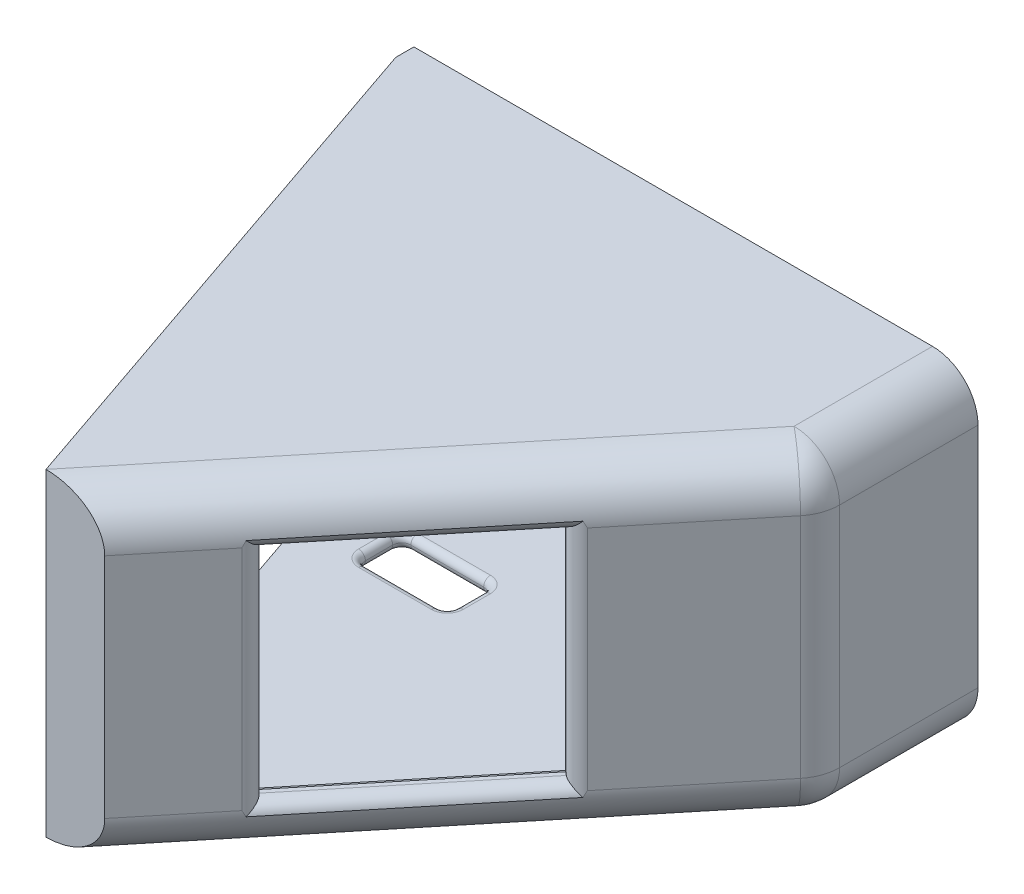
SolidWorks part; units mm, degrees
note: The reader was unsure of these and kept them because the rebuilt part matched: shared geometry of "草图1<5>".
ref_plane "前视基准面" through (0, 0, 0) normal (0, 0, 1) x (1, 0, 0)
ref_plane "上视基准面" through (0, 0, 0) normal (0, 1, 0) x (1, 0, 0)
ref_plane "右视基准面" through (0, 0, 0) normal (1, 0, 0) x (0, 0, -1)
sketch "草图1" plane through (0, 0, 0) normal (0, 0, 1) x (1, 0, 0)
  line L1 (-26, -14.5) -> (26, -14.5)
  line L2 (-26, -14.5) -> (-26, 14.5)
  line L3 (-26, 14.5) -> (26, 14.5)
  line L4 (26, -14.5) -> (26, 14.5)
  line L5 (0, 14.5) -> (0, -14.5) construction
  line L6 (-26, 0) -> (26, 0) construction
  circle A0 centre (-23.18, 11.685) radius 1.45
  circle A2 centre (-23.18, -11.685) radius 1.45
  circle A3 centre (23.18, -11.685) radius 1.45
  circle A4 centre (23.18, 11.685) radius 1.45
  point P0 (0, 0)
  dimension "D3" = 11.685
  dimension "D4" = 2.82
  dimension "D5" = 2.9
  dimension "D1" = 29
  dimension "D2" = 52
extrude "凸台-拉伸4" add sketch "草图1" along normal blind 6 contours A2 | A0 | A4 | A3
extrude "凸台-拉伸5" add sketch "草图1<5>" against normal blind 2 contours L3 L4 L1 L2
sketch "草图1<5>" plane through (0, 0, 0) normal (0, 0, 1) x (1, 0, 0) same geometry as "草图1"
sketch "草图5" plane through (0, 0, 0) normal (0, 0, 1) x (1, 0, 0)
  line L8 (-29, 17.5) -> (-29, -17.5)
  line L9 (-29, -17.5) -> (29, -17.5)
  line L10 (29, -17.5) -> (29, 17.5)
  line L11 (29, 17.5) -> (-29, 17.5)
  line L12 (-29, 17.5) -> (-29, -17.5)
  line L13 (-29, -17.5) -> (29, -17.5)
  line L14 (29, -17.5) -> (29, 17.5)
  line L15 (29, 17.5) -> (-29, 17.5)
  dimension "D1" = 3
extrude "凸台-拉伸6" add sketch "草图5" against normal blind 2
sketch "草图6" plane through (0, 0, 0) normal (0, 0, 1) x (1, 0, 0)
  line L0 (29, 17.5) -> (29, -17.5)
  line L1 (29, 17.5) -> (-29, 17.5) construction
  line L2 (-29, -17.5) -> (29, -17.5) construction
  line L3 (29, -17.5) -> (29, 17.5) construction
  line L4 (29, 17.5) -> (33, 17.5)
  line L5 (33, 17.5) -> (33, -17.5)
  line L6 (33, -17.5) -> (29, -17.5)
  line L8 (29, 17.5) -> (-29, 17.5)
  line L9 (-29, 17.5) -> (-29, -17.5)
  line L10 (-29, -17.5) -> (29, -17.5)
  line L11 (29, -17.5) -> (29, 17.5)
  line L12 (29, 17.5) -> (-29, 17.5)
  line L13 (-29, 17.5) -> (-29, -17.5)
  line L14 (-29, -17.5) -> (29, -17.5)
  line L16 (33, -17.5) -> (29, -17.5)
  line L17 (33, -17.5) -> (33, 17.5)
  line L18 (33, 17.5) -> (29, 17.5)
  line L19 (29, -17.5) -> (29, 17.5)
  dimension "D1" = 4
  dimension "D2" = 0
extrude "凸台-拉伸7" add sketch "草图6" along normal blind 12 contours L17 L16 L19 L18
fillet "圆角1" radius 1.33 1 edges at (-24.63, 11.685, 0)
fillet "圆角2" radius 1.33 1 edges at (-24.63, -11.685, 0)
fillet "圆角3" radius 1.33 1 edges at (21.73, -11.685, 0)
fillet "圆角4" radius 1.33 1 edges at (21.73, 11.685, 0)
sketch "草图11" plane through (0, 0, 12) normal (0, 0, 1) x (1, 0, 0)
  line L0 (33, -17.5) -> (29, -17.5) construction
  line L1 (33, 17.5) -> (32.1154, 17.5)
  line L2 (33, 17.5) -> (33, -17.5)
  line L3 (33, -17.5) -> (32.1154, -17.5)
  line L4 (32.1154, 17.5) -> (32.1154, -17.5)
extrude "凸台-拉伸8" add sketch "草图11" along normal blind 3
sketch "草图12" plane through (0, -17.5, 0) normal (0, -1, 0) x (-1, 0, 0)
  line L0 (-29, -12) -> (9.0007, -58.4321)
  line L1 (-33, -15) -> (2.5455, -58.4321)
  line L2 (9.0007, -58.4321) -> (2.5455, -58.4321)
  line L3 (-33, -15) -> (-32.1154, -15)
  line L4 (-32.1154, -15) -> (-32.1154, -12)
  line L5 (-32.1154, -12) -> (-29, -12)
  dimension "D1" = 60
extrude "凸台-拉伸9" add sketch "草图12" against normal through all
sketch "草图14" plane through (23.2488, 0, 19.0272) normal (-0.7739, 0, -0.6333) x (-0.6333, 0, 0.7739)
  line L0 (50.9194, -17.5) -> (-9.0806, 17.5) construction
  line L1 (-9.0806, 17.5) -> (50.9194, 17.5) construction
  line L2 (50.9194, 17.5) -> (-9.0806, -17.5) construction
  line L4 (40.9194, 14) -> (0.9194, 14)
  line L5 (40.9194, 14) -> (40.9194, -14)
  line L6 (40.9194, -14) -> (0.9194, -14)
  line L7 (0.9194, 14) -> (0.9194, -14)
  line L8 (20.9194, -14) -> (20.9194, 14) construction
  line L9 (40.9194, 0) -> (0.9194, 0) construction
  point P4 (20.9194, 0)
  dimension "D1" = 40
  dimension "D2" = 28
extrude "切除-拉伸1" cut sketch "草图14" against normal blind 1.4
sketch "草图15" plane through (24.3323, 0, 19.9139) normal (-0.7739, 0, -0.6333) x (-0.6333, 0, 0.7739)
  line L0 (40.9194, -14) -> (0.9194, 14) construction
  line L1 (0.9194, 14) -> (40.9194, 14)
  line L2 (40.9194, 14) -> (0.9194, -14) construction
  line L3 (40.9194, -14) -> (40.9194, 14) construction
  line L4 (36.0294, 14) -> (4.5294, 14)
  line L5 (36.0294, 14) -> (36.0294, -14)
  line L6 (36.0294, -14) -> (4.5294, -14)
  line L7 (4.5294, 14) -> (4.5294, -14)
  line L9 (0.9194, -14) -> (40.9194, -14) construction
  dimension "D1" = 4.89
  dimension "D2" = 31.5
extrude "切除-拉伸2" cut sketch "草图15" against normal blind 1.6 contours L5 L4 L7 L6
sketch "草图16" plane through (25.5705, 0, 20.9272) normal (-0.7739, 0, -0.6333) x (-0.6333, 0, 0.7739)
  line L0 (36.0294, 14) -> (36.0294, -14) construction
  line L1 (34.6294, 12) -> (10.6294, 12)
  line L2 (34.6294, 12) -> (34.6294, -12)
  line L3 (34.6294, -12) -> (10.6294, -12)
  line L4 (10.6294, 12) -> (10.6294, -12)
  line L5 (22.6294, -12) -> (22.6294, 12) construction
  line L6 (34.6294, 0) -> (10.6294, 0) construction
  line L7 (36.0294, 0) -> (4.5294, 0) construction
  line L8 (4.5294, 14) -> (4.5294, -14) construction
  point P0 (22.6294, 0)
  dimension "D1" = 24
  dimension "D2" = 24
  dimension "D3" = 1.4
extrude "切除-拉伸3" cut sketch "草图16" against normal through all contours L2 L1 L4 L3
sketch "草图17" plane through (24.3323, 0, 19.9139) normal (-0.7739, 0, -0.6333) x (-0.6333, 0, 0.7739)
  line L1 (40.9194, 14) -> (38.4194, 14)
  line L2 (40.9194, 14) -> (40.9194, -14)
  line L3 (40.9194, -14) -> (38.4194, -14)
  line L4 (38.4194, 14) -> (38.4194, -14)
  line L5 (40.9194, 14) -> (36.0294, 14) construction
  line L6 (36.0294, -14) -> (40.9194, -14) construction
  line L7 (40.9194, -14) -> (40.9194, 14) construction
  dimension "D1" = 2.5
extrude "切除-拉伸4" cut sketch "草图17" against normal blind 2
fillet "圆角5" radius 5 1 edges at (33, 0, 15)
sketch "草图18" plane through (0, -17.5, 0) normal (0, -1, 0) x (1, 0, 0)
  line L1 (33, 0) -> (29, 0)
  line L2 (33, 0) -> (33, -2)
  line L3 (33, -2) -> (29, -2)
  line L4 (29, 0) -> (29, -2)
extrude "凸台-拉伸10" add sketch "草图18" against normal through all
fillet "圆角6" radius 5 1 edges at (29, 0, 12)
sketch "草图19" plane through (0, -17.5, 0) normal (0, -1, 0) x (1, 0, 0)
  line L0 (-9.0007, 58.4321) -> (-29, 0)
  line L1 (-29, 0) -> (29, 0)
  line L10 (29, 10.2148) -> (29, 0)
  line L11 (29, 0) -> (-29, 0)
  line L12 (-29, 0) -> (-29, -2)
  line L13 (-29, -2) -> (33, -2)
  line L14 (33, -2) -> (33, 13.2148)
  line L15 (31.8693, 16.3815) -> (-2.5455, 58.4321)
  line L16 (-2.5455, 58.4321) -> (-9.0007, 58.4321)
  line L17 (-9.0007, 58.4321) -> (27.8693, 13.3815)
  line L18 (29, 10.2148) -> (29, 0)
  line L25 (-9.0007, 58.4321) -> (27.8693, 13.3815)
  arc A2 (29, 10.2148) -> (27.8693, 13.3815) centre (24, 10.2148) ccw
  arc A3 (33, 13.2148) -> (31.8693, 16.3815) centre (28, 13.2148) ccw
  arc A4 (29, 10.2148) -> (27.8693, 13.3815) centre (24, 10.2148) ccw
  dimension "D1" = 0
extrude "凸台-拉伸11" add sketch "草图19" against normal blind 1.5
fillet "圆角7" radius 5 4 edges at (33, -17.5, 5.6074) (32.7089, -17.5, 14.8961) (14.6619, -17.5, 37.4068) (-5.7731, -17.5, 58.4321)
fillet "圆角9" radius 1.5 4 edges at (20.3826, 0, 30.4168) (12.7825, 12, 39.7033) (12.7825, -12, 39.7033) (5.1823, 0, 48.9897)
sketch "草图22" plane through (0, 17.5, 0) normal (0, 1, 0) x (1, 0, 0)
  line L0 (-9.0007, -58.4321) -> (-29, 0)
  line L1 (-29, 0) -> (29, 0)
  line L10 (-29, 0) -> (29, 0)
  line L11 (29, 0) -> (29, -10.2148)
  line L12 (27.8693, -13.3815) -> (-9.0007, -58.4321)
  line L13 (-9.0007, -58.4321) -> (-2.5455, -58.4321)
  line L14 (-2.5455, -58.4321) -> (31.8693, -16.3815)
  line L15 (33, -13.2148) -> (33, 2)
  line L16 (33, 2) -> (-29, 2)
  line L17 (-29, 2) -> (-29, 0)
  line L18 (-29, 0) -> (29, 0)
  line L21 (-9.0007, -58.4321) -> (-2.5455, -58.4321)
  line L22 (-2.5455, -58.4321) -> (31.8693, -16.3815)
  line L23 (33, -13.2148) -> (33, 2)
  line L24 (33, 2) -> (-29, 2)
  line L25 (-29, 2) -> (-29, 0)
  arc A2 (27.8693, -13.3815) -> (29, -10.2148) centre (24, -10.2148) ccw
  arc A3 (31.8693, -16.3815) -> (33, -13.2148) centre (28, -13.2148) ccw
  arc A5 (31.8693, -16.3815) -> (33, -13.2148) centre (28, -13.2148) ccw
  dimension "D1" = 0
extrude "凸台-拉伸15" add sketch "草图22" against normal blind 1.5 contours L0 L11 L10 L1
fillet "圆角10" radius 5 7 edges at (12.7825, 13.5, 39.7033) (4.5641, 12.4393, 49.0514) (20.3209, 12.4393, 29.7986) (33, 17.5, 5.6074) (14.6619, 17.5, 37.4068) (32.7089, 17.5, 14.8961) (-5.7731, 17.5, 58.4321)
sketch "草图26" plane through (0, 0, 0) normal (0, 0, 1) x (1, 0, 0)
  line L0 (11.2453, 5.8634) -> (13.0914, 7.3757)
  line L1 (15.0126, 6.706) -> (17.2453, 5.8634)
  line L2 (17.2453, 5.8634) -> (19.0914, 7.3757)
  line L3 (19.0914, 7.3757) -> (18.7048, 9.7306)
  line L4 (18.7048, 9.7306) -> (16.472, 10.5732)
  line L5 (16.472, 10.5732) -> (14.6259, 9.0609)
  line L6 (14.6259, 9.0609) -> (15.0126, 6.706)
  line L7 (9.0126, 6.706) -> (11.2453, 5.8634)
  line L8 (8.6259, 9.0609) -> (9.0126, 6.706)
  line L9 (10.472, 10.5732) -> (8.6259, 9.0609)
  line L10 (12.7048, 9.7306) -> (10.472, 10.5732)
  line L11 (13.0914, 7.3757) -> (12.7048, 9.7306)
  line L12 (5.2453, 5.8634) -> (7.0914, 7.3757)
  line L13 (3.0126, 6.706) -> (5.2453, 5.8634)
  line L14 (2.6259, 9.0609) -> (3.0126, 6.706)
  line L15 (4.472, 10.5732) -> (2.6259, 9.0609)
  line L16 (6.7048, 9.7306) -> (4.472, 10.5732)
  line L17 (7.0914, 7.3757) -> (6.7048, 9.7306)
  line L18 (-0.7547, 5.8634) -> (1.0914, 7.3757)
  line L19 (-2.9874, 6.706) -> (-0.7547, 5.8634)
  line L20 (-3.3741, 9.0609) -> (-2.9874, 6.706)
  line L21 (-1.528, 10.5732) -> (-3.3741, 9.0609)
  line L22 (0.7048, 9.7306) -> (-1.528, 10.5732)
  line L23 (1.0914, 7.3757) -> (0.7048, 9.7306)
  line L24 (-6.7547, 5.8634) -> (-4.9086, 7.3757)
  line L25 (-8.9874, 6.706) -> (-6.7547, 5.8634)
  line L26 (-9.3741, 9.0609) -> (-8.9874, 6.706)
  line L27 (-7.528, 10.5732) -> (-9.3741, 9.0609)
  line L28 (-5.2952, 9.7306) -> (-7.528, 10.5732)
  line L29 (-4.9086, 7.3757) -> (-5.2952, 9.7306)
  line L30 (-12.7547, 5.8634) -> (-10.9086, 7.3757)
  line L31 (-14.9874, 6.706) -> (-12.7547, 5.8634)
  line L32 (-15.3741, 9.0609) -> (-14.9874, 6.706)
  line L33 (-13.528, 10.5732) -> (-15.3741, 9.0609)
  line L34 (-11.2952, 9.7306) -> (-13.528, 10.5732)
  line L35 (-10.9086, 7.3757) -> (-11.2952, 9.7306)
  line L36 (11.2453, 0.8634) -> (13.0914, 2.3757)
  line L37 (9.0126, 1.706) -> (11.2453, 0.8634)
  line L38 (8.6259, 4.0609) -> (9.0126, 1.706)
  line L39 (10.472, 5.5732) -> (8.6259, 4.0609)
  line L40 (12.7048, 4.7306) -> (10.472, 5.5732)
  line L41 (13.0914, 2.3757) -> (12.7048, 4.7306)
  line L42 (5.2453, 0.8634) -> (7.0914, 2.3757)
  line L43 (3.0126, 1.706) -> (5.2453, 0.8634)
  line L44 (2.6259, 4.0609) -> (3.0126, 1.706)
  line L45 (4.472, 5.5732) -> (2.6259, 4.0609)
  line L46 (6.7048, 4.7306) -> (4.472, 5.5732)
  line L47 (7.0914, 2.3757) -> (6.7048, 4.7306)
  line L48 (-0.7547, 0.8634) -> (1.0914, 2.3757)
  line L49 (-2.9874, 1.706) -> (-0.7547, 0.8634)
  line L50 (-3.3741, 4.0609) -> (-2.9874, 1.706)
  line L51 (-1.528, 5.5732) -> (-3.3741, 4.0609)
  line L52 (0.7048, 4.7306) -> (-1.528, 5.5732)
  line L53 (1.0914, 2.3757) -> (0.7048, 4.7306)
  line L54 (-6.7547, 0.8634) -> (-4.9086, 2.3757)
  line L55 (-8.9874, 1.706) -> (-6.7547, 0.8634)
  line L56 (-9.3741, 4.0609) -> (-8.9874, 1.706)
  line L57 (-7.528, 5.5732) -> (-9.3741, 4.0609)
  line L58 (-5.2952, 4.7306) -> (-7.528, 5.5732)
  line L59 (-4.9086, 2.3757) -> (-5.2952, 4.7306)
  line L60 (-12.7547, 0.8634) -> (-10.9086, 2.3757)
  line L61 (-14.9874, 1.706) -> (-12.7547, 0.8634)
  line L62 (-15.3741, 4.0609) -> (-14.9874, 1.706)
  line L63 (-13.528, 5.5732) -> (-15.3741, 4.0609)
  line L64 (-11.2952, 4.7306) -> (-13.528, 5.5732)
  line L65 (-10.9086, 2.3757) -> (-11.2952, 4.7306)
  line L66 (11.2453, -4.1366) -> (13.0914, -2.6243)
  line L67 (9.0126, -3.294) -> (11.2453, -4.1366)
  line L68 (8.6259, -0.9391) -> (9.0126, -3.294)
  line L69 (10.472, 0.5732) -> (8.6259, -0.9391)
  line L70 (12.7048, -0.2694) -> (10.472, 0.5732)
  line L71 (13.0914, -2.6243) -> (12.7048, -0.2694)
  line L72 (5.2453, -4.1366) -> (7.0914, -2.6243)
  line L73 (3.0126, -3.294) -> (5.2453, -4.1366)
  line L74 (2.6259, -0.9391) -> (3.0126, -3.294)
  line L75 (4.472, 0.5732) -> (2.6259, -0.9391)
  line L76 (6.7048, -0.2694) -> (4.472, 0.5732)
  line L77 (7.0914, -2.6243) -> (6.7048, -0.2694)
  line L78 (-0.7547, -4.1366) -> (1.0914, -2.6243)
  line L79 (-2.9874, -3.294) -> (-0.7547, -4.1366)
  line L80 (-3.3741, -0.9391) -> (-2.9874, -3.294)
  line L81 (-1.528, 0.5732) -> (-3.3741, -0.9391)
  line L82 (0.7048, -0.2694) -> (-1.528, 0.5732)
  line L83 (1.0914, -2.6243) -> (0.7048, -0.2694)
  line L84 (-6.7547, -4.1366) -> (-4.9086, -2.6243)
  line L85 (-8.9874, -3.294) -> (-6.7547, -4.1366)
  line L86 (-9.3741, -0.9391) -> (-8.9874, -3.294)
  line L87 (-7.528, 0.5732) -> (-9.3741, -0.9391)
  line L88 (-5.2952, -0.2694) -> (-7.528, 0.5732)
  line L89 (-4.9086, -2.6243) -> (-5.2952, -0.2694)
  line L90 (-12.7547, -4.1366) -> (-10.9086, -2.6243)
  line L91 (-14.9874, -3.294) -> (-12.7547, -4.1366)
  line L92 (-15.3741, -0.9391) -> (-14.9874, -3.294)
  line L93 (-13.528, 0.5732) -> (-15.3741, -0.9391)
  line L94 (-11.2952, -0.2694) -> (-13.528, 0.5732)
  line L95 (-10.9086, -2.6243) -> (-11.2952, -0.2694)
  line L96 (11.2453, -9.1366) -> (13.0914, -7.6243)
  line L97 (9.0126, -8.294) -> (11.2453, -9.1366)
  line L98 (8.6259, -5.9391) -> (9.0126, -8.294)
  line L99 (10.472, -4.4268) -> (8.6259, -5.9391)
  line L100 (12.7048, -5.2694) -> (10.472, -4.4268)
  line L101 (13.0914, -7.6243) -> (12.7048, -5.2694)
  line L102 (5.2453, -9.1366) -> (7.0914, -7.6243)
  line L103 (3.0126, -8.294) -> (5.2453, -9.1366)
  line L104 (2.6259, -5.9391) -> (3.0126, -8.294)
  line L105 (4.472, -4.4268) -> (2.6259, -5.9391)
  line L106 (6.7048, -5.2694) -> (4.472, -4.4268)
  line L107 (7.0914, -7.6243) -> (6.7048, -5.2694)
  line L108 (-0.7547, -9.1366) -> (1.0914, -7.6243)
  line L109 (-2.9874, -8.294) -> (-0.7547, -9.1366)
  line L110 (-3.3741, -5.9391) -> (-2.9874, -8.294)
  line L111 (-1.528, -4.4268) -> (-3.3741, -5.9391)
  line L112 (0.7048, -5.2694) -> (-1.528, -4.4268)
  line L113 (1.0914, -7.6243) -> (0.7048, -5.2694)
  line L114 (-6.7547, -9.1366) -> (-4.9086, -7.6243)
  line L115 (-8.9874, -8.294) -> (-6.7547, -9.1366)
  line L116 (-9.3741, -5.9391) -> (-8.9874, -8.294)
  line L117 (-7.528, -4.4268) -> (-9.3741, -5.9391)
  line L118 (-5.2952, -5.2694) -> (-7.528, -4.4268)
  line L119 (-4.9086, -7.6243) -> (-5.2952, -5.2694)
  line L120 (-12.7547, -9.1366) -> (-10.9086, -7.6243)
  line L121 (-14.9874, -8.294) -> (-12.7547, -9.1366)
  line L122 (-15.3741, -5.9391) -> (-14.9874, -8.294)
  line L123 (-13.528, -4.4268) -> (-15.3741, -5.9391)
  line L124 (-11.2952, -5.2694) -> (-13.528, -4.4268)
  line L125 (-10.9086, -7.6243) -> (-11.2952, -5.2694)
  line L126 (17.2453, 0.8634) -> (19.0914, 2.3757)
  line L127 (15.0126, 1.706) -> (17.2453, 0.8634)
  line L128 (14.6259, 4.0609) -> (15.0126, 1.706)
  line L129 (16.472, 5.5732) -> (14.6259, 4.0609)
  line L130 (18.7048, 4.7306) -> (16.472, 5.5732)
  line L131 (19.0914, 2.3757) -> (18.7048, 4.7306)
  line L132 (17.2453, -4.1366) -> (19.0914, -2.6243)
  line L133 (15.0126, -3.294) -> (17.2453, -4.1366)
  line L134 (14.6259, -0.9391) -> (15.0126, -3.294)
  line L135 (16.472, 0.5732) -> (14.6259, -0.9391)
  line L136 (18.7048, -0.2694) -> (16.472, 0.5732)
  line L137 (19.0914, -2.6243) -> (18.7048, -0.2694)
  line L138 (17.2453, -9.1366) -> (19.0914, -7.6243)
  line L139 (15.0126, -8.294) -> (17.2453, -9.1366)
  line L140 (14.6259, -5.9391) -> (15.0126, -8.294)
  line L141 (16.472, -4.4268) -> (14.6259, -5.9391)
  line L142 (18.7048, -5.2694) -> (16.472, -4.4268)
  line L143 (19.0914, -7.6243) -> (18.7048, -5.2694)
  circle A0 centre (16.8587, 8.2183) radius 2.0667 construction
  dimension "D1" = 6
  dimension "D2" = 4
extrude "切除-拉伸5" cut sketch "草图26" against normal blind 10
sketch "草图27" plane through (23.2488, 0, 19.0272) normal (-0.7739, 0, -0.6333) x (-0.6333, 0, 0.7739)
  line L1 (0.9194, 5) -> (-2.0806, 5)
  line L2 (0.9194, 5) -> (0.9194, -5)
  line L3 (0.9194, -5) -> (-2.0806, -5)
  line L4 (-2.0806, 5) -> (-2.0806, -5)
  line L6 (0.9194, 14) -> (0.9194, -14) construction
  point P10 (0.9194, 0)
  point P11 (0.9194, 0)
  dimension "D1" = 10
  dimension "D2" = 3
extrude "凸台-拉伸16" add sketch "草图27" along normal blind 3
sketch "草图28" plane through (-0.5823, 0, 0.7115) normal (-0.6333, 0, 0.7739) x (0.7739, 0, 0.6333)
  line L1 (30.0424, 5) -> (27.0424, 5)
  line L2 (30.0424, 5) -> (30.0424, -5)
  line L3 (30.0424, -5) -> (27.0424, -5)
  line L4 (27.0424, 5) -> (27.0424, -5)
extrude "凸台-拉伸17" add sketch "草图28" along normal blind 3
fillet "圆角16" radius 1 1 edges at (23.6166, -5, 18.5779)
fillet "圆角17" radius 1 1 edges at (23.6166, 5, 18.5779)
fillet "圆角18" radius 0.5 1 edges at (24.5666, 0, 17.4171)
sketch "草图31" plane through (0, -17.5, 0) normal (0, -1, 0) x (1, 0, 0)
  line L0 (-29, -2) -> (28, -2) construction
  line L1 (-16, 16.3302) -> (-8, 16.3302)
  line L2 (-17, 15.3302) -> (-17, 12.3302)
  line L3 (-16, 11.3302) -> (-8, 11.3302)
  line L4 (-7, 15.3302) -> (-7, 12.3302)
  line L5 (28, -2) -> (28, 13.2148) construction
  arc A0 (-16, 11.3302) -> (-17, 12.3302) centre (-16, 12.3302) cw
  arc A1 (-8, 11.3302) -> (-7, 12.3302) centre (-8, 12.3302) ccw
  arc A2 (-8, 16.3302) -> (-7, 15.3302) centre (-8, 15.3302) cw
  arc A3 (-17, 15.3302) -> (-16, 16.3302) centre (-16, 15.3302) cw
  dimension "D2" = 1
  dimension "D1" = 35
extrude "切除-拉伸6" cut sketch "草图31" against normal blind 15 contours L2 A0 L3 A1 L4 A2 L1 A3
fillet "圆角19" radius 0.75 16 edges at (-16.7071, -16, 11.6231) (-17, -16, 13.8302) (-16.7071, -16, 16.0373) (-12, -16, 16.3302) (-7.2929, -16, 16.0373) (-7, -16, 13.8302) (-7.2929, -16, 11.6231) (-16.7071, -17.5, 11.6231) (-17, -17.5, 13.8302) (-16.7071, -17.5, 16.0373) (-12, -17.5, 16.3302) (-7.2929, -17.5, 16.0373) (-7, -17.5, 13.8302) (-7.2929, -17.5, 11.6231) (-12, -16, 11.3302) (-12, -17.5, 11.3302)
